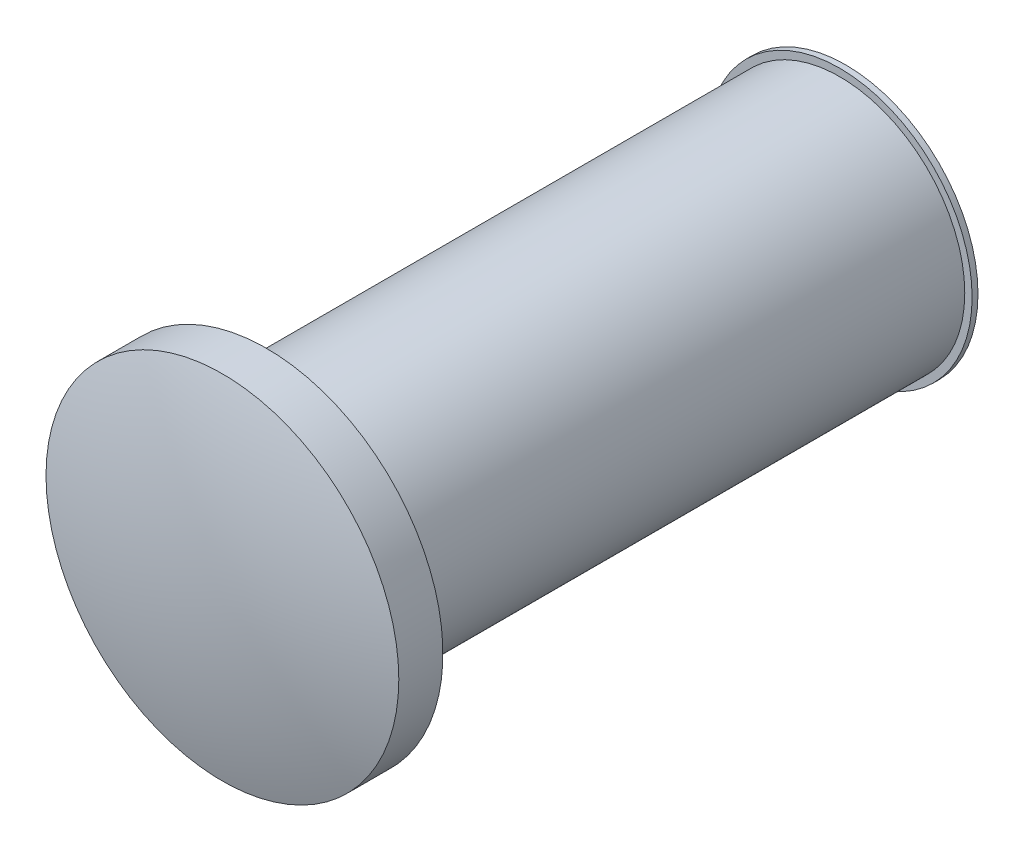
SolidWorks part; units mm, degrees
material "AISI 316 Stainless Steel Sheet (SS)"
ref_plane "Front Plane" through (0, 0, 0) normal (0, 0, 1) x (1, 0, 0)
ref_plane "Top Plane" through (0, 0, 0) normal (0, 1, 0) x (1, 0, 0)
ref_plane "Right Plane" through (0, 0, 0) normal (1, 0, 0) x (0, 0, -1)
sketch "Sketch1" plane through (0, 0, 0) normal (0, 0, 1) x (1, 0, 0)
  circle A0 centre (0, 0) radius 1.0795
  dimension "D1" = 2.159
extrude "Boss-Extrude1" add sketch "Sketch1" along normal blind 4.953 contours A0
sketch "Sketch2" plane through (0, 0, 4.953) normal (0, 0, 1) x (1, 0, 0)
  circle A0 centre (0, 0) radius 1.524
  dimension "D1" = 3.048
extrude "Boss-Extrude2" add sketch "Sketch2" along normal blind 0.381
dome "Dome1" faces to dome 1 distance 0.2286 reverse direction no elliptical dome no face at (1.524, 0, 5.334) parameters "D1"=0.2286
sketch "Sketch3" plane through (0, 0, 0) normal (0, 0, -1) x (-1, 0, 0)
  circle A0 centre (0, 0) radius 1.143
  dimension "D1" = 2.286
extrude "Boss-Extrude3" add sketch "Sketch3" along normal blind 0.0508
sketch "Sketch4" plane through (0, 0, -0.0508) normal (0, 0, -1) x (-1, 0, 0)
  circle A0 centre (0, 0) radius 1.0668
  dimension "D1" = 2.1336
extrude "Cut-Extrude1" cut sketch "Sketch4" against normal blind 0.127
